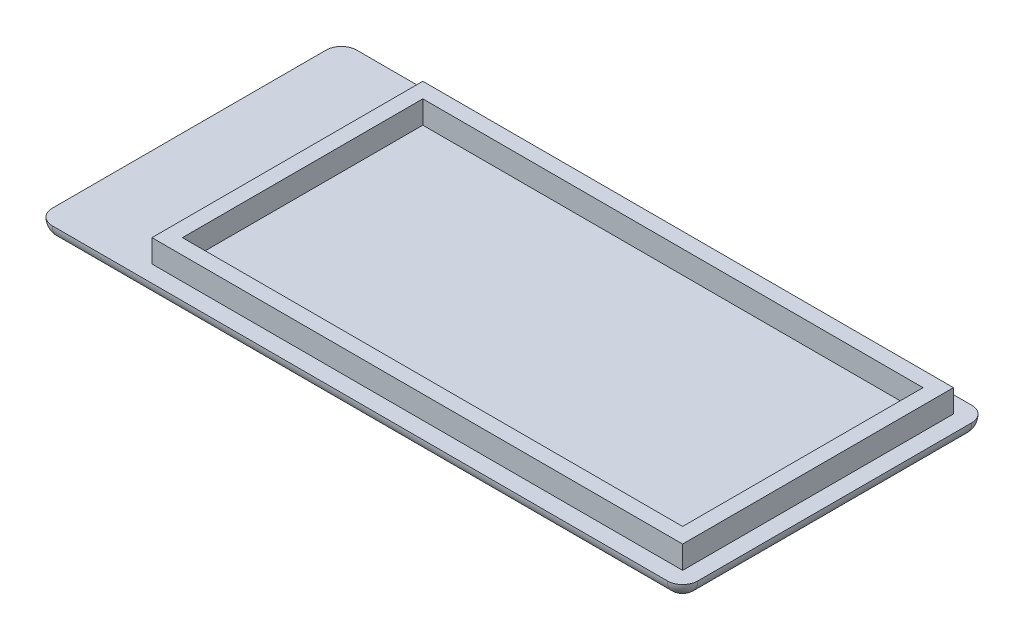
SolidWorks part; units mm, degrees
ref_plane "Front Plane" through (0, 0, 0) normal (0, 0, 1) x (1, 0, 0)
ref_plane "Top Plane" through (0, 0, 0) normal (0, 1, 0) x (1, 0, 0)
ref_plane "Right Plane" through (0, 0, 0) normal (1, 0, 0) x (0, 0, -1)
sketch "Sketch1" plane through (0, 0, 0) normal (0, 0, 1) x (1, 0, 0)
  line L1 (0, 0) -> (42.4256, 0)
  line L2 (0, 0) -> (0, 1)
  line L3 (0, 1) -> (42.4256, 1)
  line L4 (42.4256, 0) -> (42.4256, 1)
  dimension "D1" = 1
  dimension "D2" = 42.4256
extrude "Boss-Extrude1" add sketch "Sketch1" along normal blind 20
fillet "Fillet1" radius 1 4 edges at (42.4256, 0, 10) (21.2128, 0, 0) (0, 0, 10) (21.2128, 0, 20)
sketch "Sketch2" plane through (0, 1, 0) normal (0, 1, 0) x (1, 0, 0)
  line L0 (7.4514, -2.1) -> (7.4514, -17.9)
  line L1 (6.4514, -1.1) -> (41.3256, -1.1)
  line L2 (6.4514, -1.1) -> (6.4514, -18.9)
  line L3 (6.4514, -18.9) -> (41.3256, -18.9)
  line L4 (41.3256, -1.1) -> (41.3256, -18.9)
  line L5 (7.4514, -17.9) -> (40.3256, -17.9)
  line L6 (40.3256, -2.1) -> (40.3256, -17.9)
  line L7 (7.4514, -2.1) -> (40.3256, -2.1)
  line L8 (41.4256, 0) -> (1, 0) construction
  line L9 (42.4256, -19) -> (42.4256, -1) construction
  line L10 (41.4256, -20) -> (1, -20) construction
  dimension "D2" = 1.1
  dimension "D3" = 1.1
  dimension "D4" = 1.1
  dimension "D5" = 34.8742
  dimension "D1" = 1
extrude "Boss-Extrude2" add sketch "Sketch2" along normal blind 1.5
